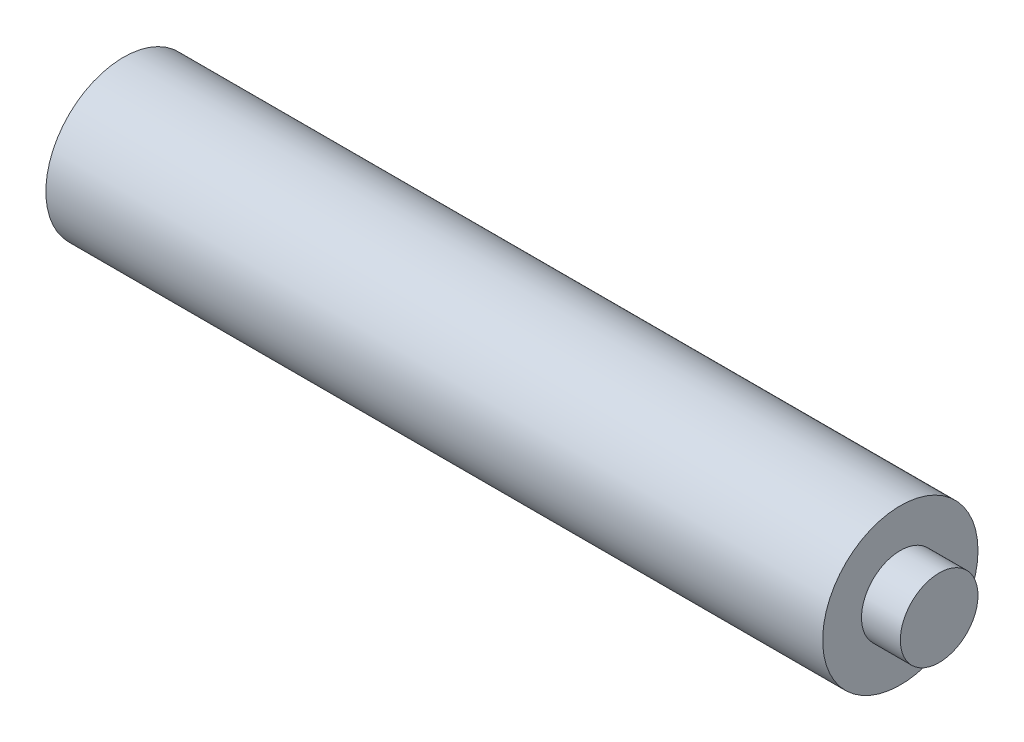
SolidWorks part; units mm, degrees
ref_plane "Front Plane" through (0, 0, 0) normal (0, 0, 1) x (1, 0, 0)
ref_plane "Top Plane" through (0, 0, 0) normal (0, 1, 0) x (1, 0, 0)
ref_plane "Right Plane" through (0, 0, 0) normal (1, 0, 0) x (0, 0, -1)
sketch "Sketch1" plane through (0, 0, 0) normal (1, 0, 0) x (0, 0, -1)
  circle A0 centre (0, 0) radius 4
  dimension "D1" = 8
extrude "Boss-Extrude1" add sketch "Sketch1" along normal mid plane 40
sketch "Sketch2" plane through (20, 0, 0) normal (1, 0, 0) x (0, 0, -1)
  circle A0 centre (0, 0) radius 2
  dimension "D1" = 4
extrude "Boss-Extrude2" add sketch "Sketch2" along normal blind 2
